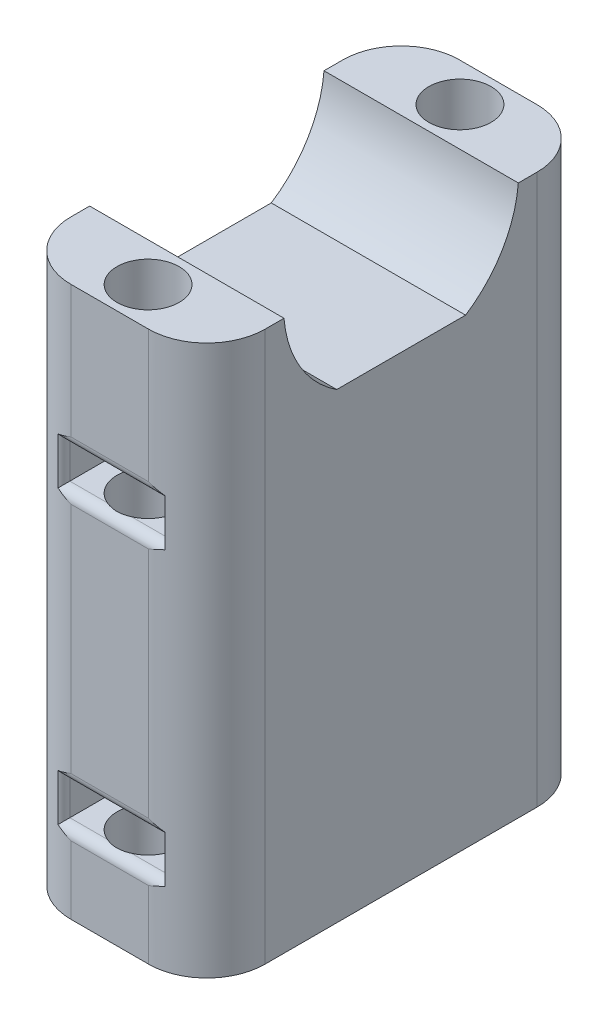
SolidWorks part; units mm, degrees
ref_plane "Front Plane" through (0, 0, 0) normal (0, 0, 1) x (1, 0, 0)
ref_plane "Top Plane" through (0, 0, 0) normal (0, 1, 0) x (1, 0, 0)
ref_plane "Right Plane" through (0, 0, 0) normal (1, 0, 0) x (0, 0, -1)
sketch "Sketch1" plane through (0, 0, 0) normal (1, 0, 0) x (0, 0, -1)
  line L0 (10, 0) -> (-10, 0)
  line L1 (-10, 0) -> (-10, 28.8)
  line L2 (-10, 28.8) -> (-6.05, 28.8)
  line L3 (-3.315, 23.7661) -> (3.315, 23.7661)
  line L4 (6.05, 28.8) -> (10, 28.8)
  line L5 (10, 28.8) -> (10, 0)
  arc A0 (-6.05, 28.8) -> (-3.315, 23.7661) centre (-0.05, 28.8) ccw
  arc A1 (3.315, 23.7661) -> (6.05, 28.8) centre (0.05, 28.8) ccw
  point P4 (0, 0)
  point P12 (0, 23.7661)
  dimension "D3" = 6
  dimension "D1" = 6.63
  dimension "D2" = 20
  dimension "D4" = 12.1
  dimension "D5" = 28.8
extrude "Boss-Extrude1" add sketch "Sketch1" along normal mid plane 10
sketch "Sketch2" plane through (0, 28.8, 0) normal (0, 1, 0) x (1, 0, 0)
  circle A0 centre (0, 8.025) radius 1.6
  circle A1 centre (0, -8.025) radius 1.6
  circle A2 centre (0, 8.025) radius 1.6 construction
  circle A3 centre (0, -8.025) radius 1.6 construction
extrude "Cut-Extrude1" cut sketch "Sketch2" against normal through all
ref_plane "Plane1" through (0, 20, 0) normal (0, -1, 0) x (-1, 0, 0)
sketch "Sketch3" plane through (0, 20, 0) normal (0, -1, 0) x (-1, 0, 0)
  line L0 (-5, 10) -> (5, 10) construction
  line L1 (0, 5.0805) -> (2.55, 6.5528)
  line L2 (2.55, 6.5528) -> (2.55, 10)
  line L5 (-2.55, 10) -> (-2.55, 6.5528)
  line L6 (-2.55, 6.5528) -> (0, 5.0805)
  line L13 (0.7059, 11.377) -> (-1.7526, 9.9576) [skipped]
  line L14 (3.2559, 9.0897) -> (0.7974, 10.5091) [skipped]
  line L15 (-2.55, 10) -> (2.55, 10)
  line L16 (5, 7) -> (5, -7) construction
  circle A0 centre (0, 8.025) radius 2.55 construction
  dimension "D1" = 5.1
extrude "Cut-Extrude2" cut sketch "Sketch3" against normal mid plane 2
mirror "Mirror13" about plane through (0, 0, 0) normal (0, 0, 1) of "Cut-Extrude2"
ref_plane "Plane3" through (0, 12.5, 0) normal (0, -1, 0) x (-1, 0, 0)
mirror "Mirror14" about plane through (0, 12.5, 0) normal (0, -1, 0) of "Mirror13", "Cut-Extrude2"
sketch "Sketch5" plane through (-5, 0, 0) normal (-1, 0, 0) x (0, 0, 1)
  line L0 (10, 28.8) -> (10, 0) construction
  line L1 (-10, 28.8) -> (10, 28.8)
  line L2 (-10, 28.8) -> (-10, 28.3)
  line L3 (-10, 28.3) -> (10, 28.3)
  line L4 (10, 28.8) -> (10, 28.3)
  dimension "D1" = 0.5
extrude "Cut-Extrude4" cut sketch "Sketch5" against normal through all
fillet "Fillet2" radius 0.5 16 edges at (-2.55, 20, -10) (0, 19, -10) (2.55, 20, -10) (0, 21, -10) (0, 4, -10) (2.55, 5, -10) (0, 6, -10) (-2.55, 5, -10) (2.55, 5, 10) (0, 4, 10) (-2.55, 5, 10) (0, 6, 10) (-2.55, 20, 10) (0, 19, 10) (2.55, 20, 10) (0, 21, 10)
fillet "Fillet3" radius 3 4 edges at (-5, 14.15, 10) (5, 14.15, 10) (5, 14.15, -10) (-5, 14.15, -10)
